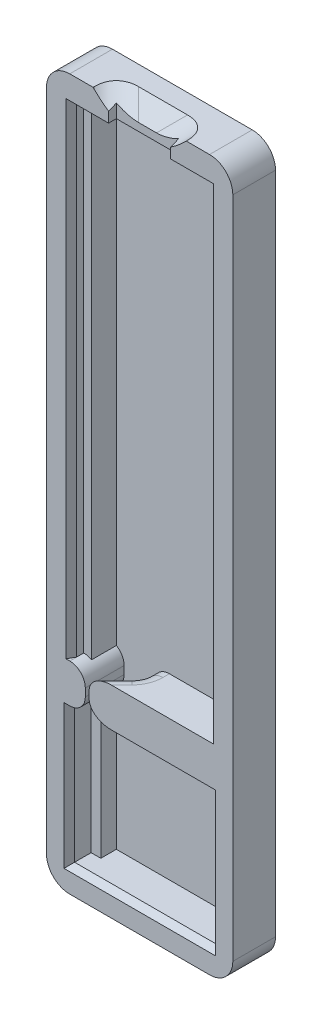
SolidWorks part; units mm, degrees
ref_plane "Front Plane" through (0, 0, 0) normal (0, 0, 1) x (1, 0, 0)
ref_plane "Top Plane" through (0, 0, 0) normal (0, 1, 0) x (1, 0, 0)
ref_plane "Right Plane" through (0, 0, 0) normal (1, 0, 0) x (0, 0, -1)
sketch "Sketch1" plane through (0, 0, 0) normal (0, 0, 1) x (1, 0, 0)
  line L0 (6, 10) -> (6, 6) construction
  line L1 (9, 72.5) -> (-9, 72.5) construction
  line L2 (9, 72.5) -> (9, 10) construction
  line L3 (9, 10) -> (-9, 10) construction
  line L4 (-9, 72.5) -> (-9, 10) construction
  line L5 (-9.25, 5) -> (9.25, 5) construction
  line L6 (-9.25, 5) -> (-9.25, -13) construction
  line L7 (-9.25, -13) -> (9.25, -13) construction
  line L8 (9.25, 5) -> (9.25, -13) construction
  line L9 (6, 6) -> (-6, 6) construction
  line L10 (-6, 6) -> (-6, 10) construction
  line L12 (-12, 75.5) -> (12, 75.5)
  line L13 (-12, 75.5) -> (-12, -16)
  line L14 (-12, -16) -> (12, -16)
  line L15 (12, 75.5) -> (12, -16)
  point P12 (0, 6)
  point P13 (0, 10)
  point P15 (0, 5)
  point P20 (0, 75.5)
  point P21 (0, 72.5)
  dimension "D1" = 18
  dimension "D2" = 18.5
  dimension "D3" = 62.5
  dimension "D4" = 18
  dimension "D5" = 12
  dimension "D6" = 4
  dimension "D7" = 5
  dimension "D8" = 5
  dimension "D9" = 3
  dimension "D10" = 3
  dimension "D11" = 24
sketch "Sketch2" plane through (0, 0, 0) normal (0, 0, 1) x (1, 0, 0)
  line L1 (-9, 75.5) -> (9, 75.5)
  line L2 (-12, 72.5) -> (-12, -13)
  line L3 (-9, -16) -> (9, -16)
  line L4 (12, 72.5) -> (12, -13)
  arc A0 (-12, -13) -> (-9, -16) centre (-9, -13) ccw
  arc A1 (9, -16) -> (12, -13) centre (9, -13) ccw
  arc A2 (9, 75.5) -> (12, 72.5) centre (9, 72.5) cw
  arc A3 (-9, 75.5) -> (-12, 72.5) centre (-9, 72.5) ccw
  point P10 (12, -16)
  point P15 (-12, 75.5)
  dimension "D1" = 3
extrude "Boss-Extrude1" add sketch "Sketch2" along normal blind 5.5
sketch "Sketch4" plane through (0, 0, 5.5) normal (0, 0, 1) x (1, 0, 0)
  line L0 (-12, 75.5) -> (12, 75.5) construction
  line L1 (-8, 72.5) -> (8, 72.5)
  line L2 (-8, 72.5) -> (-8, 10)
  line L3 (-8, 10) -> (8, 10)
  line L4 (8, 72.5) -> (8, 10)
  line L5 (-9, 72.5) -> (-9, 10) construction
  line L6 (9, 72.5) -> (-9, 72.5) construction
  line L7 (-9.25, 5) -> (9.25, 5) construction
  line L8 (-8, 5) -> (8, 5)
  line L9 (-8, 5) -> (-8, -13)
  line L10 (-8, -13) -> (8, -13)
  line L11 (8, 5) -> (8, -13)
  line L12 (-9.25, -13) -> (9.25, -13) construction
  point P4 (0, 72.5)
  point P7 (0, 75.5)
  point P9 (-8, 41.25)
  point P12 (-9, 41.25)
  point P22 (0, 5)
  dimension "D1" = 1
extrude "Cut-Extrude1" cut sketch "Sketch4" against normal blind 5
sketch "Sketch5" plane through (0, 0, 5.5) normal (0, 0, 1) x (1, 0, 0)
  line L5 (-9.25, 5) -> (9.25, 5)
  line L6 (-9.25, 5) -> (-9.25, -13)
  line L7 (-9.25, -13) -> (9.25, -13)
  line L8 (9.25, 5) -> (9.25, -13)
extrude "Cut-Extrude2" cut sketch "Sketch5" against normal blind 3
sketch "Sketch7" plane through (0, 0, 5.5) normal (0, 0, 1) x (1, 0, 0)
  line L1 (-9, 72.5) -> (9, 72.5)
  line L2 (-9, 72.5) -> (-9, 10)
  line L3 (-9, 10) -> (9, 10)
  line L4 (9, 72.5) -> (9, 10)
extrude "Cut-Extrude3" cut sketch "Sketch7" against normal blind 1.8
sketch "Sketch10" plane through (0, 72.5, 0) normal (0, -1, 0) x (1, 0, 0)
  line L0 (9, 5.5) -> (-9, 5.5) construction
  line L1 (-4, 4.5) -> (4, 4.5)
  line L2 (-4, 4.5) -> (-4, 5.5)
  line L3 (-4, 5.5) -> (4, 5.5)
  line L4 (4, 4.5) -> (4, 5.5)
  point P6 (0, 4.5)
  dimension "D1" = 1
  dimension "D2" = 8
extrude "Cut-Extrude4" cut sketch "Sketch10" against normal through all draft 45 and the other way blind 1.8 from offset 1 draft outward yes offset against normal yes
fillet "Fillet1" radius 4 2 edges at (5, 74.5, 3.5) (-5, 74.5, 3.5)
chamfer "Chamfer1" distance 0.5 angle 60 5 edges at (9, 41.25, 5.5) (-9, 41.25, 5.5) (9.25, -4, 5.5) (0, -13, 5.5) (-9.25, -4, 5.5) first distance on face at (0, -4, 5.5)
sketch "Sketch11" plane through (0, 10, 0) normal (0, 1, 0) x (1, 0, 0)
  line L0 (-7, -5.5) -> (-7, -0.5)
  line L1 (-6, -5.5) -> (-9, -5.5) construction
  line L2 (-7, -0.5) -> (-3.1699, -0.5)
  line L3 (-3.1699, -0.5) -> (-3.1699, -1.3415)
  line L4 (-3.7557, -2.7557) -> (-6.5, -5.5)
  line L5 (-5.8284, -5.5) -> (-4, -5.5) construction
  line L6 (-6.5, -5.5) -> (-7, -5.5)
  arc A0 (-3.1699, -1.3415) -> (-3.7557, -2.7557) centre (-5.1699, -1.3415) cw
  dimension "D5" = 2
  dimension "D1" = 5
  dimension "D2" = 45
  dimension "D3" = 0.5
  dimension "D4" = 7
extrude "Cut-Extrude5" cut sketch "Sketch11" against normal up to next
fillet "Fillet2" radius 2 6 edges at (-5.1278, 5, 4.1278) (-5.1278, 10, 4.1278) (-3.1699, 5, 0.9207) (-3.3221, 5, 2.1068) (-3.1699, 10, 0.9207) (-3.3221, 10, 2.1068)
fillet "Fillet3" radius 2 2 edges at (-7, 10, 3) (-7, 5, 3)
